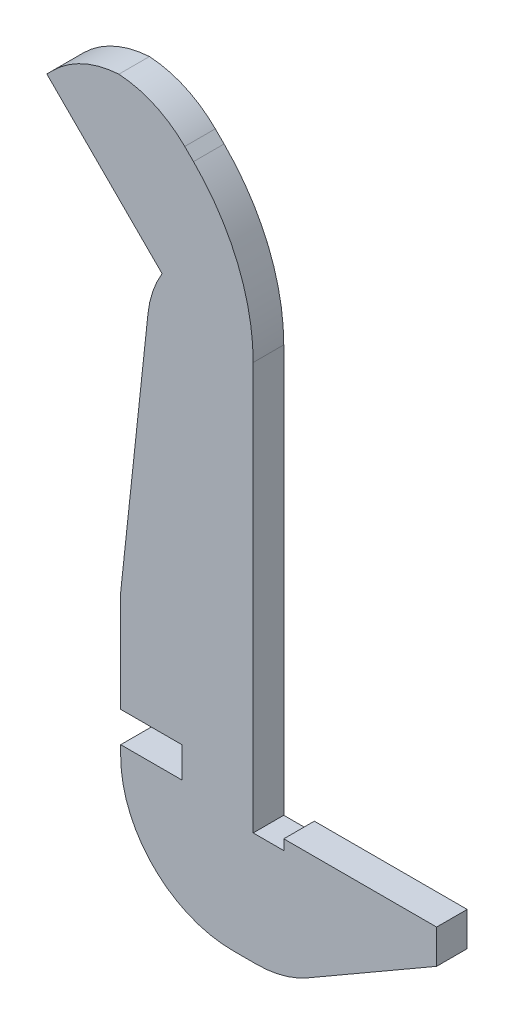
SolidWorks part; units mm, degrees
material "PBT General Purpose"
ref_plane "Front Plane" through (0, 0, 0) normal (0, 0, 1) x (1, 0, 0)
ref_plane "Top Plane" through (0, 0, 0) normal (0, 1, 0) x (1, 0, 0)
ref_plane "Right Plane" through (0, 0, 0) normal (1, 0, 0) x (0, 0, -1)
sketch "Sketch1" plane through (0, 0, 0) normal (0, 0, 1) x (1, 0, 0)
  line L0 (0, 0) -> (-1.5, 0)
  line L1 (-1.5, 0) -> (-1.5, -0.1)
  line L2 (-1.5, -0.1) -> (-1.8, -0.1)
  line L3 (-1.8, -0.1) -> (-1.8, 3.1)
  line L5 (-2.8, 4.1) -> (-2.8, -1.2) construction
  line L6 (-2.8, -1.2) -> (-1.5, -1.2)
  line L7 (-1.5, -1.2) -> (0, -0.334)
  line L8 (0, -0.334) -> (0, 0)
  line L9 (-1.8, 3.1) -> (-2.8, 4.1) construction
  line L11 (-1.8, 3.1) -> (1.15, 0.15) construction
  line L13 (-1.8, 3.1) -> (-1.8, 3.5172)
  line L14 (-2.8, 4.1) -> (-2.6939, 4.2061)
  line L15 (-1.8, 3.5172) -> (-1.8, 4.7263)
  line L16 (-1.8, 4.7263) -> (-2.7646, 5.691)
  line L17 (-2.7646, 5.691) -> (-3.4718, 5.691)
  line L18 (-3.4718, 5.691) -> (-3.8253, 5.3374)
  line L20 (-2.6939, 4.2061) -> (-3.8253, 5.3374)
  line L21 (0, 0) -> (0, 0.15) construction
  line L22 (0, 0.15) -> (1.15, 0.15) construction
  line L24 (-3.1, -1.2) -> (-3.1, 1.3)
  line L25 (-3.1, 1.3) -> (-2.8, 4.1)
  line L26 (-2.8, -1.2) -> (-3.1, -1.2)
  point P11 (-1.65, -0.1)
  dimension "D1" = 1.5
  dimension "D2" = 0.1
  dimension "D3" = 0.3
  dimension "D6" = 120
  dimension "D7" = 1.1
  dimension "D8" = 1
  dimension "D9" = 45
  dimension "D12" = 0.5
  dimension "D13" = 1
  dimension "D10" = 1.6
  dimension "D11" = 0.15
  dimension "D14" = 1
  dimension "D4" = 0.15
  dimension "D5" = 1.15
  dimension "D15" = 45
  dimension "D18" = 2.5
  dimension "D16" = 0.3
extrude "Boss-Extrude1" add sketch "Sketch1" along normal mid plane 0.3 contours L6 L7 L8 L0 L1 L2 L3 L13 L15 L16 L17 L18 L20 L14 L25 L24 L26
fillet "Fillet1" radius 1.1 1 edges at (-3.1, -1.2, 0)
sketch "Sketch2" plane through (0, 0, 0.15) normal (0, 0, 1) x (1, 0, 0)
  line L0 (-3.1, 0) -> (-2.5, 0)
  line L2 (-2.5, 0) -> (-2.5, 0.3)
  line L3 (-2.5, 0.3) -> (-3.1, 0.3)
  line L4 (-3.1, 0.3) -> (-3.1, 0)
  line L5 (0, 0) -> (-1.5, 0) construction
  line L6 (-3.1, -0.1) -> (-3.1, 1.3) construction
  dimension "D1" = 0.6
  dimension "D2" = 0.3
extrude "Cut-Extrude1" cut sketch "Sketch2" against normal through all
fillet "Fillet2" radius 2 1 edges at (-1.8, 4.7263, 0)
fillet "Fillet3" radius 1 4 edges at (-2.8, 4.1, 0) (-1.5, -1.2, 0) (-3.4718, 5.691, 0) (-2.7646, 5.691, 0)
equation "\"t\"= 0.3'thickness of the sheets"
equation "\"FlexJoint\"= 0.15'Width of flextures"
equation "\"FoldJoint\"= 0.4'Width of folding joints"
equation "\"AssembleAngle\"= 90'Angle of assembly parts"
equation "\"D1@Boss-Extrude1\"=\"t\""
equation "\"D11@Sketch1\"=\"t\"/2"
equation "\"D4@Sketch1\"=\"FlexJoint\""
equation "\"D5@Sketch1\"=\"FlexJoint\"+1"
